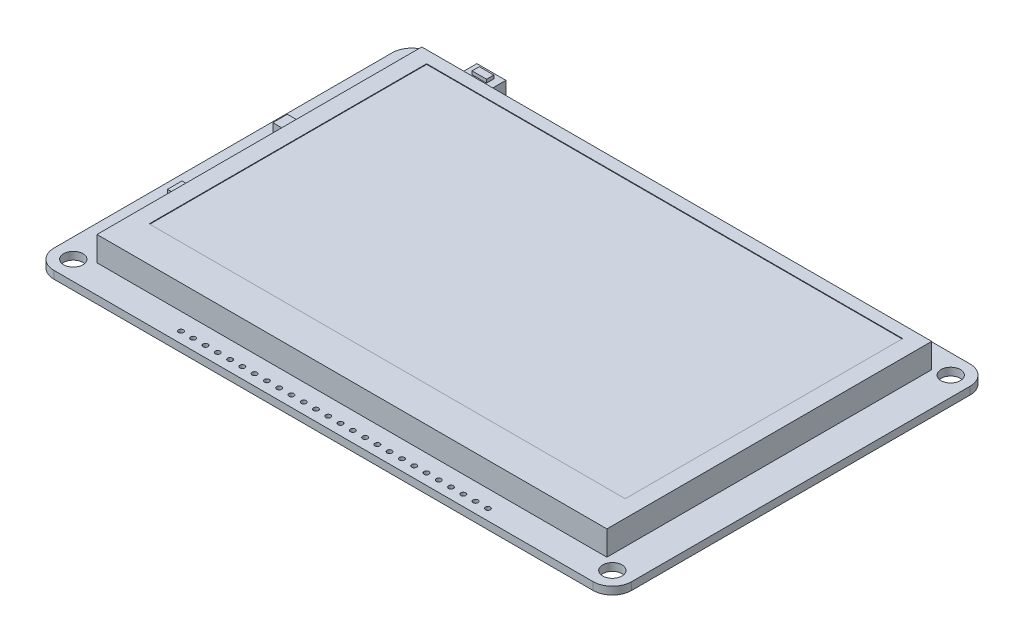
SolidWorks part; units mm, degrees
ref_plane "Front Plane" through (0, 0, 0) normal (0, 0, 1) x (1, 0, 0)
ref_plane "Top Plane" through (0, 0, 0) normal (0, 1, 0) x (1, 0, 0)
ref_plane "Right Plane" through (0, 0, 0) normal (1, 0, 0) x (0, 0, -1)
ref_axis "Axis X" through (-88.99, 0, 0) along (1, 0, 0)
ref_axis "Axis Y" through (0, 55, 0) along (0, -1, 0)
ref_axis "Axis Z" through (0, 0, -88.99) along (0, 0, 1)
sketch "Sketch1" plane through (0, 0, 0) normal (0, 1, 0) x (1, 0, 0)
  line L1 (-59.7662, -39.0017) -> (59.7662, -39.0017)
  line L2 (-59.7662, -39.0017) -> (-59.7662, 39.0017)
  line L3 (-59.7662, 39.0017) -> (59.7662, 39.0017)
  line L4 (59.7662, -39.0017) -> (59.7662, 39.0017)
  line L5 (-59.7662, -39.0017) -> (59.7662, 39.0017) construction
  line L6 (-59.7662, 39.0017) -> (59.7662, -39.0017) construction
  point P0 (0, 0)
  dimension "D1" = 119.5324
  dimension "D2" = 78.0034
extrude "Boss-Extrude1" add sketch "Sketch1" along normal blind 1.5875
sketch "Sketch2" plane through (0, 1.5875, 0) normal (0, 1, 0) x (1, 0, 0)
  line L0 (0, 0) -> (-86.9901, 0) construction
  line L1 (-0.8731, 0) -> (0.8731, 0) construction
  line L2 (0, 0) -> (0, 75.5139) construction
  line L3 (0, -0.8731) -> (0, 0.8731) construction
  circle A0 centre (-55.7657, 35.0012) radius 2
  circle A1 centre (-55.7657, -35.0012) radius 2
  circle A2 centre (55.7657, 35.0012) radius 2
  circle A3 centre (55.7657, -35.0012) radius 2
  dimension "D1" = 111.5314
  dimension "D2" = 70.0024
  dimension "D3" = 4
extrude "Cut-Extrude1" cut sketch "Sketch2" against normal up to next
sketch "Sketch3" plane through (0, 1.5875, 0) normal (0, 1, 0) x (1, 0, 0)
  line L0 (0, 0) -> (-104.3039, 0) construction
  line L1 (-0.8731, 0) -> (0.8731, 0) construction
  circle A0 centre (-31.7373, 36.758) radius 0.508
  circle A1 centre (-55.7657, 35.0012) radius 2 construction
  circle A2 centre (-31.7373, -36.758) radius 0.508
  dimension "D1" = 1.016
  dimension "D2" = 24.0284
  dimension "D3" = 72.5
extrude "Cut-Extrude2" cut sketch "Sketch3" against normal up to next
sketch "Sketch11" plane through (0, 1.5875, 0) normal (0, 1, 0) x (1, 0, 0)
  line L0 (-59.7662, 39.0017) -> (-59.7662, -39.0017) construction
  line L1 (59.7662, 39.0017) -> (-59.7662, 39.0017) construction
  line L2 (-59.7662, 35.0012) -> (-59.7662, 39.0017)
  line L3 (-59.7662, 39.0017) -> (-55.7657, 39.0017)
  line L4 (0, 0) -> (-80.7962, 0) construction
  line L5 (-0.8731, 0) -> (0.8731, 0) construction
  line L6 (-59.7662, -39.0017) -> (-55.7657, -39.0017)
  line L7 (-59.7662, -35.0012) -> (-59.7662, -39.0017)
  line L8 (0, 0) -> (0, 58.3461) construction
  line L9 (59.7662, -35.0012) -> (59.7662, -39.0017)
  line L10 (59.7662, -39.0017) -> (55.7657, -39.0017)
  line L11 (59.7662, 39.0017) -> (55.7657, 39.0017)
  line L12 (59.7662, 35.0012) -> (59.7662, 39.0017)
  arc A0 (-59.7662, 35.0012) -> (-55.7657, 39.0017) centre (-55.7657, 35.0012) cw
  circle A1 centre (-55.7657, 35.0012) radius 2 construction
  arc A2 (-59.7662, -35.0012) -> (-55.7657, -39.0017) centre (-55.7657, -35.0012) ccw
  arc A3 (59.7662, -35.0012) -> (55.7657, -39.0017) centre (55.7657, -35.0012) cw
  arc A4 (59.7662, 35.0012) -> (55.7657, 39.0017) centre (55.7657, 35.0012) ccw
extrude "Cut-Extrude4" cut sketch "Sketch11" against normal up to next
pattern_linear "LPattern1" count 26 spacing 2.54 along (1, 0, 0) of "Cut-Extrude2"
sketch "Sketch4" plane through (0, 1.5875, 0) normal (0, 1, 0) x (1, 0, 0)
  line L0 (-29.6321, 0) -> (32.8636, 0) construction
  line L1 (-0.8731, 0) -> (0.8731, 0) construction
  text T0 "Screen This Side"
sketch "Sketch5" plane through (0, 1.5875, 0) normal (0, 1, 0) x (1, 0, 0)
  line L0 (-59.7662, 35.0012) -> (-59.7662, -35.0012) construction
  line L1 (-52.6662, 34.0017) -> (52.8338, 34.0017)
  line L2 (-52.6662, 34.0017) -> (-52.6662, -33.1983)
  line L3 (-52.6662, -33.1983) -> (52.8338, -33.1983)
  line L4 (52.8338, 34.0017) -> (52.8338, -33.1983)
  line L5 (55.7657, 39.0017) -> (-55.7657, 39.0017) construction
  dimension "D1" = 105.5
  dimension "D2" = 67.2
  dimension "D3" = 7.1
  dimension "D4" = 5
extrude "Boss-Extrude2" add sketch "Sketch5" along normal blind 5.08
sketch "Sketch6" plane through (0, 6.6675, 0) normal (0, 1, 0) x (1, 0, 0)
  line L0 (-49.1662, -25.8983) -> (49.3338, 31.5017) construction
  line L1 (-49.1662, 31.5017) -> (49.3338, 31.5017)
  line L2 (-49.1662, 31.5017) -> (-49.1662, -25.8983)
  line L3 (-49.1662, -25.8983) -> (49.3338, -25.8983)
  line L4 (49.3338, 31.5017) -> (49.3338, -25.8983)
  line L5 (-52.6662, 34.0017) -> (-52.6662, -33.1983) construction
  line L6 (52.8338, 34.0017) -> (-52.6662, 34.0017) construction
  dimension "D1" = 57.4
  dimension "D2" = 3.5
  dimension "D3" = 2.5
  dimension "D4" = 98.5
extrude "Cut-Extrude3" cut sketch "Sketch6" against normal blind 0.127
sketch "Sketch7" plane through (0, 1.5875, 0) normal (0, 1, 0) x (1, 0, 0)
  line L0 (-59.7662, 35.0012) -> (-59.7662, -35.0012) construction
  line L1 (-45.2662, 38.0017) -> (-39.2662, 38.0017)
  line L2 (-45.2662, 38.0017) -> (-45.2662, 34.5017)
  line L3 (-45.2662, 34.5017) -> (-39.2662, 34.5017)
  line L4 (-39.2662, 38.0017) -> (-39.2662, 34.5017)
  line L5 (55.7657, 39.0017) -> (-55.7657, 39.0017) construction
  dimension "D1" = 3.5
  dimension "D2" = 6
  dimension "D3" = 14.5
  dimension "D4" = 1
extrude "Boss-Extrude3" add sketch "Sketch7" along normal blind 3.8
sketch "Sketch8" plane through (0, 5.3875, 0) normal (0, 1, 0) x (1, 0, 0)
  line L0 (-45.2662, 36.2517) -> (-39.2662, 36.2517) construction
  line L1 (-43.7662, 37.0017) -> (-40.7662, 37.0017)
  line L2 (-43.7662, 37.0017) -> (-43.7662, 35.5017)
  line L3 (-43.7662, 35.5017) -> (-40.7662, 35.5017)
  line L4 (-40.7662, 37.0017) -> (-40.7662, 35.5017)
  line L5 (-43.7662, 37.0017) -> (-40.7662, 35.5017) construction
  line L6 (-43.7662, 35.5017) -> (-40.7662, 37.0017) construction
  line L7 (-45.2662, 38.0017) -> (-45.2662, 34.5017) construction
  line L8 (-39.2662, 34.5017) -> (-39.2662, 38.0017) construction
  point P0 (-42.2662, 36.2517)
  dimension "D1" = 3
  dimension "D2" = 1.5
extrude "Boss-Extrude4" add sketch "Sketch8" along normal offset from surface (0.7 mm away) 4.5 up to face at (0.0838, 1.5875, -0.4017) offset beyond the face yes
sketch "Sketch9" plane through (0, 1.5875, 0) normal (0, 1, 0) x (1, 0, 0)
  line L0 (-59.7662, 35.0012) -> (-59.7662, -35.0012) construction
  line L1 (-57.8862, 11.4017) -> (-54.8862, 11.4017)
  line L2 (-57.8862, 11.4017) -> (-57.8862, 8.4017)
  line L3 (-57.8862, 8.4017) -> (-54.8862, 8.4017)
  line L4 (-54.8862, 11.4017) -> (-54.8862, 8.4017)
  line L5 (-57.8862, 11.4017) -> (-54.8862, 8.4017) construction
  line L6 (-57.8862, 8.4017) -> (-54.8862, 11.4017) construction
  line L7 (55.7657, 39.0017) -> (-55.7657, 39.0017) construction
  point P0 (-56.3862, 9.9017)
  dimension "D1" = 3
  dimension "D2" = 3
  dimension "D3" = 1.88
  dimension "D4" = 27.6
extrude "Boss-Extrude5" add sketch "Sketch9" along normal blind 1.71
sketch "Sketch10" plane through (0, 1.5875, 0) normal (0, 1, 0) x (1, 0, 0)
  line L0 (-59.7662, 35.0012) -> (-59.7662, -35.0012) construction
  line L1 (-57.5462, -10.7417) -> (-54.5462, -10.7417)
  line L2 (-57.5462, -10.7417) -> (-57.5462, -13.7417)
  line L3 (-57.5462, -13.7417) -> (-54.5462, -13.7417)
  line L4 (-54.5462, -10.7417) -> (-54.5462, -13.7417)
  line L5 (-57.5462, -10.7417) -> (-54.5462, -13.7417) construction
  line L6 (-57.5462, -13.7417) -> (-54.5462, -10.7417) construction
  line L7 (-55.7657, -39.0017) -> (55.7657, -39.0017) construction
  point P0 (-56.0462, -12.2417)
  dimension "D1" = 3
  dimension "D2" = 3
  dimension "D3" = 2.22
  dimension "D4" = 25.26
extrude "Boss-Extrude6" add sketch "Sketch10" along normal blind 1
